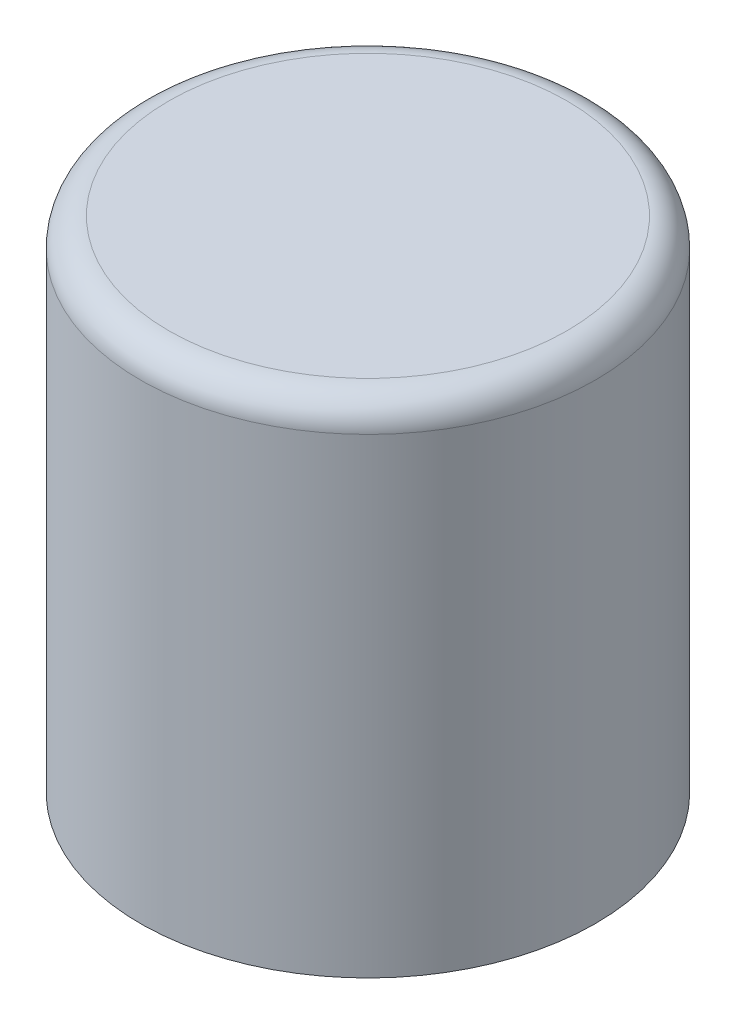
SolidWorks part; units mm, degrees
ref_plane "Plan de face" through (0, 0, 0) normal (0, 0, 1) x (1, 0, 0)
ref_plane "Plan de dessus" through (0, 0, 0) normal (0, 1, 0) x (1, 0, 0)
ref_plane "Plan de droite" through (0, 0, 0) normal (1, 0, 0) x (0, 0, -1)
sketch "Esquisse1" plane through (0, 0, 0) normal (0, 0, 1) x (1, 0, 0)
  line L0 (0, 0) -> (0, 35.1) construction
  line L1 (-12.5, 3.8574) -> (-12.5, 6.3) construction
  line L2 (-16, 0) -> (-16, 35.1)
  line L3 (-16, 35.1) -> (0, 35.1)
  line L4 (0, 35.1) -> (0, 32.1)
  line L5 (0, 32.1) -> (-11.5, 32.1) construction
  line L21 (-12.5, 32.1) -> (0, 32.1)
  line L22 (-12.5, 6.3) -> (-12.5, 3)
  line L23 (-12.5, 3) -> (-9, 3)
  line L24 (-9, 3) -> (-9, 0)
  line L25 (-9, 0) -> (-12.5, 0)
  line L26 (-16, 0) -> (-12.5, 0)
  line L27 (-12.5, 6.3) -> (-9, 6.3)
  line L28 (-9, 6.3) -> (-9, 9.3)
  line L29 (-9, 9.3) -> (-12.5, 9.3)
  line L30 (-12.5, 9.3) -> (-12.5, 12.6)
  line L31 (-12.5, 12.6) -> (-12.5, 32.1)
  point P4 (-9, 7.7347)
  point P15 (-12.5, 22.35)
  dimension "D1" = 3.5
  dimension "D2" = 3.3
  dimension "D3" = 9
  dimension "D4" = 3
  dimension "D5" = 3.5
  dimension "D6" = 19.5
  dimension "D7" = 16
  dimension "D8" = 32.1
  dimension "D9" = 3
revolve "Révolution1" add sketch "Esquisse1" angle 360 about L0
fillet "Congé1" radius 2 1 edges at (16, 35.1, 0)
